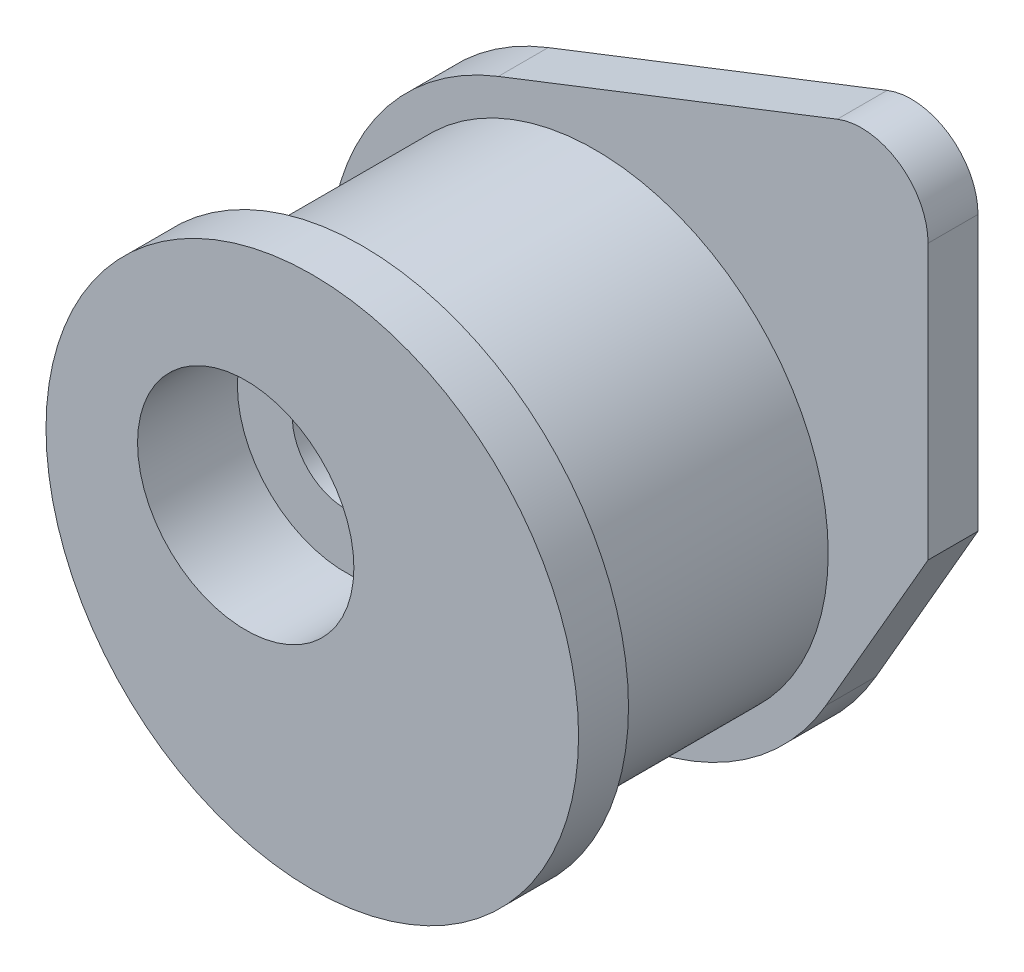
SolidWorks part; units mm, degrees
ref_plane "Front Plane" through (0, 0, 0) normal (0, 0, 1) x (1, 0, 0)
ref_plane "Top Plane" through (0, 0, 0) normal (0, 1, 0) x (1, 0, 0)
ref_plane "Right Plane" through (0, 0, 0) normal (1, 0, 0) x (0, 0, -1)
sketch "Sketch1" plane through (0, 0, 0) normal (0, 0, 1) x (1, 0, 0)
  line L0 (10, 21.7336) -> (10, -20.9549) construction
  circle A0 centre (0, 0) radius 1.6
  circle A1 centre (2, -1) radius 8
  dimension "D3" = 3.2
  dimension "D4" = 16
  dimension "D1" = 1
  dimension "D2" = 10
  dimension "D5" = 2
extrude "Boss-Extrude1" add sketch "Sketch1" along normal blind 10
sketch "Sketch2" plane through (0, 0, 10) normal (0, 0, 1) x (1, 0, 0)
  circle A0 centre (0, 0) radius 3.25
  dimension "D1" = 6.5
extrude "Cut-Extrude1" cut sketch "Sketch2" against normal blind 3
ref_axis "Axis1" through (2, -1, 10) along (0, 0, -1)
ref_plane "Plane1" through (0, -1, 0) normal (0, 1, 0) x (1, 0, 0)
sketch "Sketch3" plane through (0, -1, 0) normal (0, 1, 0) x (1, 0, 0)
  line L1 (-11.505, -1.5) -> (-5, -1.5)
  line L2 (-11.505, -1.5) -> (-11.505, -8.5)
  line L3 (-11.505, -8.5) -> (-5, -8.5)
  line L4 (-5, -1.5) -> (-5, -8.5)
  line L5 (2, 0) -> (2, -10.0175) construction
  line L7 (-5, -5) -> (2, -5.0087) construction
  line L8 (2, -10) -> (2, 0) construction
  dimension "D1" = 7
  dimension "D2" = 7
revolve "Cut-Revolve1" cut sketch "Sketch3" angle 360 about L5
sketch "Sketch4" plane through (0, 0, 0) normal (0, 0, 1) x (1, 0, 0)
  line L0 (12, 16.7357) -> (12, -8.5352) construction
  line L1 (-0.9111, 6.4516) -> (12, 11.4955)
  line L2 (12, 11.4955) -> (12, 0.3243)
  line L3 (12, 0.3243) -> (8.9294, -4.9979)
  circle A0 centre (2, -1) radius 8 construction
  arc A1 (-0.9111, 6.4516) -> (8.9294, -4.9979) centre (2, -1) cw
  dimension "D1" = 12
extrude "Boss-Extrude2" add sketch "Sketch4" along normal up to surface (1.5 mm away) up to face at (-5, -1, 1.5)
fillet "Fillet1" radius 2 1 edges at (12, 11.4955, 0.75)
